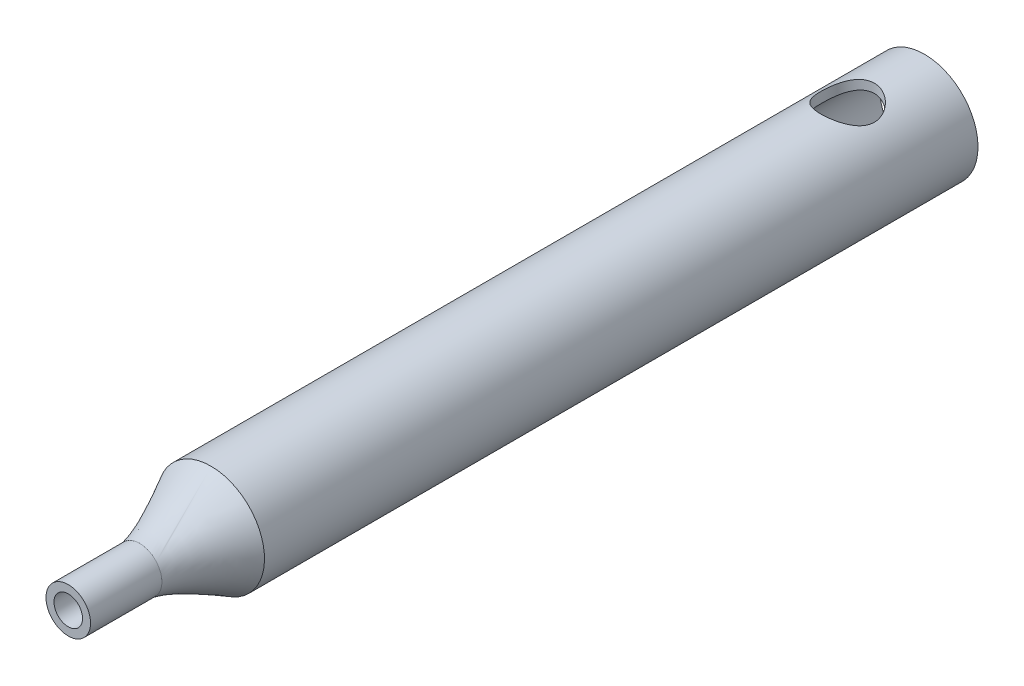
SolidWorks part; units mm, degrees
ref_plane "Front Plane" through (0, 0, 0) normal (0, 0, 1) x (1, 0, 0)
ref_plane "Top Plane" through (0, 0, 0) normal (0, 1, 0) x (1, 0, 0)
ref_plane "Right Plane" through (0, 0, 0) normal (1, 0, 0) x (0, 0, -1)
sketch "Sketch2" plane through (0, 0, 0) normal (0, 0, 1) x (1, 0, 0)
  circle A0 centre (0, 0) radius 30
  circle A1 centre (0, 0) radius 25
  dimension "D1" = 60
  dimension "D2" = 50
extrude "Boss-Extrude1" add sketch "Sketch2" along normal blind 400
ref_plane "Plane1" through (0, 0, 440) normal (0, 0, 1) x (1, 0, 0)
sketch "Sketch3" plane through (0, 0, 440) normal (0, 0, 1) x (1, 0, 0)
  circle A0 centre (0, 0) radius 12.5
  circle A1 centre (0, 0) radius 8
  dimension "D1" = 25
  dimension "D2" = 16
sketch "Sketch7" plane through (0, 0, 400) normal (0, 0, 1) x (1, 0, 0)
  circle A0 centre (0, 0) radius 25
  circle A1 centre (0, 0) radius 30
loft "Loft3" add section "Sketch7" section "Sketch3" connector at (0.2073, 29.9993, 400) connector at (9.3816, 8.2605, 440)
loft "Cut-Loft1" cut section "Sketch7<3>" section "Sketch3<7>" connector at (15.2481, -19.8115, 400) connector at (7.9015, -1.2515, 440)
sketch "Sketch7<3>" plane through (0, 0, 400) normal (0, 0, 1) x (1, 0, 0) same geometry as "Sketch7"
sketch "Sketch3<7>" plane through (0, 0, 440) normal (0, 0, 1) x (1, 0, 0) same geometry as "Sketch3"
extrude "Boss-Extrude2" add sketch "Sketch3<8>" along normal blind 40
sketch "Sketch3<8>" plane through (0, 0, 440) normal (0, 0, 1) x (1, 0, 0) same geometry as "Sketch3"
sketch "Sketch8" plane through (0, 0, 0) normal (0, 1, 0) x (1, 0, 0)
  circle A0 centre (0, -43.1148) radius 15
  dimension "D1" = 30
extrude "Cut-Extrude1" cut sketch "Sketch8" along normal blind 40
